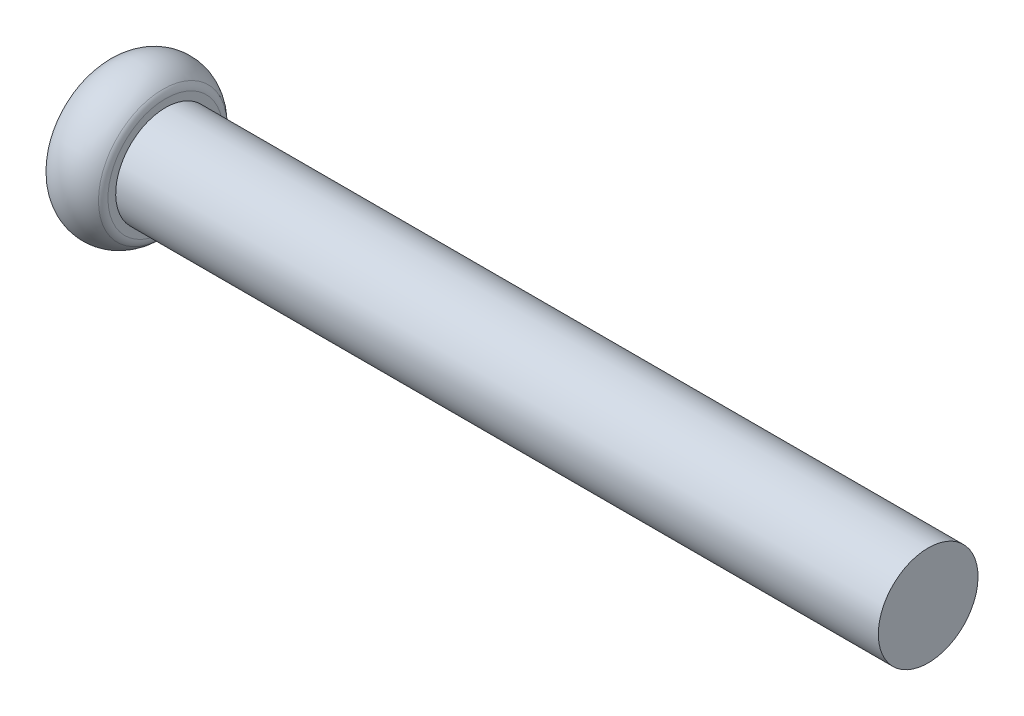
SolidWorks part; units mm, degrees
material "Plain Carbon Steel"
ref_plane "Front Plane" through (0, 0, 0) normal (0, 0, 1) x (1, 0, 0)
ref_plane "Top Plane" through (0, 0, 0) normal (0, 1, 0) x (1, 0, 0)
ref_plane "Right Plane" through (0, 0, 0) normal (1, 0, 0) x (0, 0, -1)
sketch "Sketch1" plane through (0, 0, 0) normal (0, 0, 1) x (1, 0, 0)
  line L0 (22.1448, 0) -> (-4.1395, 0) construction
  line L1 (1.3019, 1) -> (16.6, 1)
  line L2 (16.6, 1) -> (16.6, 0)
  line L3 (0, 0) -> (0, 0.7935)
  line L5 (16.6, 0) -> (0, 0)
  line L6 (1.3019, 1) -> (1.3019, 1.2266)
  arc A0 (0.1132, 1.1846) -> (0, 0.7935) centre (0.7322, 0.7935) ccw
  arc A1 (0.1132, 1.1846) -> (1.3019, 1.2266) centre (0.7219, 0.8) cw
  dimension "D6" = 0.7322
  dimension "D7" = 0.72
  dimension "D1" = 16.6
  dimension "D2" = 1
  dimension "D3" = 15.2981
  dimension "D4" = 0.7935
  dimension "D5" = 0.2266
revolve "Revolve1" add sketch "Sketch1" angle 360 about L0
cosmetic thread "Cosmetic Thread1" parameters "D1"=13, "D2"=1.5
sketch "Sketch2" plane through (0, 0, 0) normal (-1, 0, 0) x (0, 0, 1)
  line L0 (-0.3, -1.175) -> (0.3, -1.175)
  line L1 (-0.3, -1.175) -> (-0.3, 1.175)
  line L2 (0.3, 1.175) -> (-0.3, 1.175)
  line L3 (0.3, 1.175) -> (0.3, -1.175)
  line L4 (0.3, 0) -> (-0.3, 0) construction
  dimension "D1" = 2.35
  dimension "D2" = 0.6
sketch "Sketch3" plane through (1.3019, 0, 0) normal (1, 0, 0) x (0, 0, -1)
  line L0 (0.35, -0.442) -> (-0.35, -0.442)
  line L1 (0.35, -0.442) -> (0.35, 0.442)
  line L2 (-0.35, 0.442) -> (0.35, 0.442)
  line L3 (-0.35, 0.442) -> (-0.35, -0.442)
  line L6 (0.35, 0) -> (-0.35, 0) construction
  dimension "D1" = 0.884
  dimension "D2" = 0.7
loft "Cut-Loft1" cut profiles "Sketch2", "Sketch3" connector at (0, -1.175, 0.3) connector at (1.3019, -0.442, 0.35)
pattern_circular "CirPattern1" count 2 over 90 about axis through (22.1448, 0, 0) along (-1, 0, 0) of "Cut-Loft1"
fillet "Fillet1" radius 0.2 1 edges at (1.3019, 1.2266, 0)
